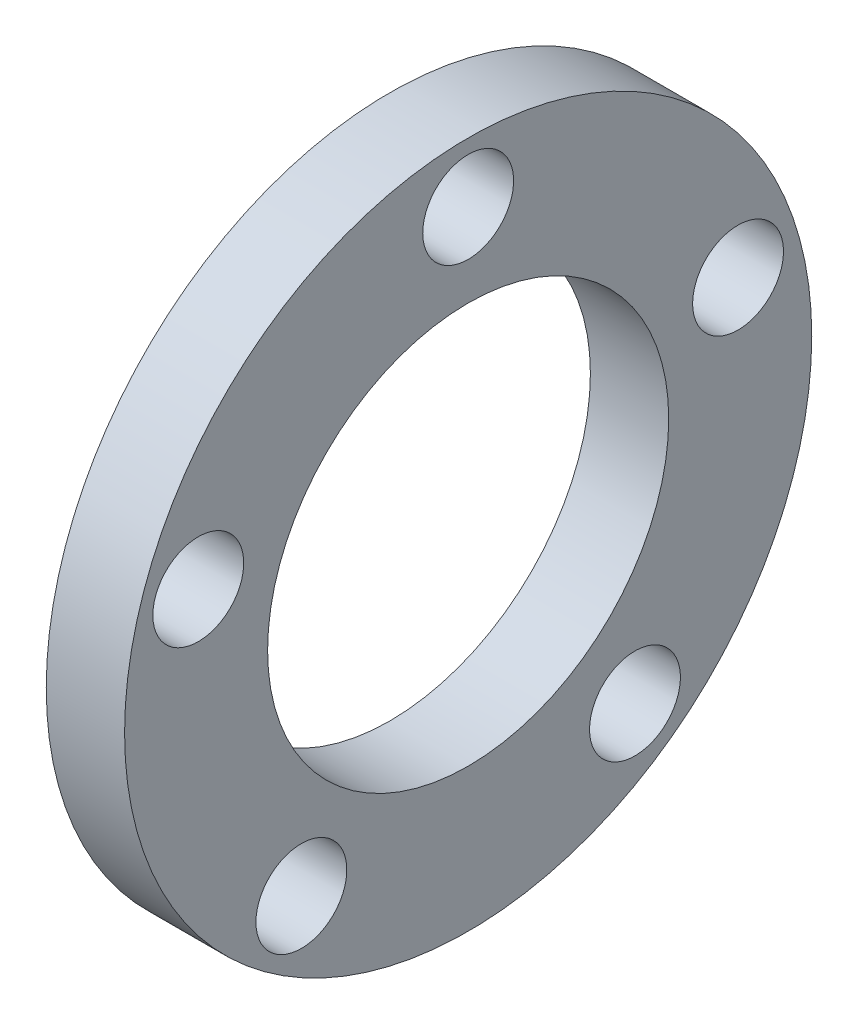
SolidWorks part; units mm, degrees
material "6061 Alloy"
ref_plane "Front Plane" through (0, 0, 0) normal (0, 0, 1) x (1, 0, 0)
ref_plane "Top Plane" through (0, 0, 0) normal (0, 1, 0) x (1, 0, 0)
ref_plane "Right Plane" through (0, 0, 0) normal (1, 0, 0) x (0, 0, -1)
sketch "Sketch1" plane through (0, 0, 0) normal (1, 0, 0) x (0, 0, -1)
  circle A0 centre (0, 0) radius 13.9245
  circle A1 centre (0, 0) radius 8.128
  dimension "D1" = 16.256
  dimension "D2" = 27.8489
extrude "Boss-Extrude1" add sketch "Sketch1" along normal blind 3.175
sketch "Sketch2" plane through (0, 0, 0) normal (-1, 0, 0) x (0, 0, 1)
  line L0 (0, 0) -> (0, 11.5) construction
  circle A0 centre (0, 11.5) radius 1.8415
  circle A1 centre (10.9371, 3.5537) radius 1.8415
  circle A2 centre (6.7595, -9.3037) radius 1.8415
  circle A3 centre (-6.7595, -9.3037) radius 1.8415
  circle A4 centre (-10.9371, 3.5537) radius 1.8415
  point P14 (0, 0)
  dimension "D1" = 5
  dimension "D2" = 3.683
  dimension "D3" = 11.5
extrude "Cut-Extrude1" cut sketch "Sketch2" against normal through all
sketch "Sketch3" [suppressed] plane through (0, 0, 0) normal (0, 1, 0) x (1, 0, 0)
  line L0 (0, 0) -> (10.16, 0) construction
  line L1 (0, 13.9245) -> (0, -13.9245) construction
  line L2 (10.16, -13.9245) -> (10.16, 13.9245) construction
  circle A0 centre (5.08, 0) radius 1.397
  dimension "D1" = 2.794
extrude "Cut-Extrude2" [suppressed] cut sketch "Sketch3" against normal through all
